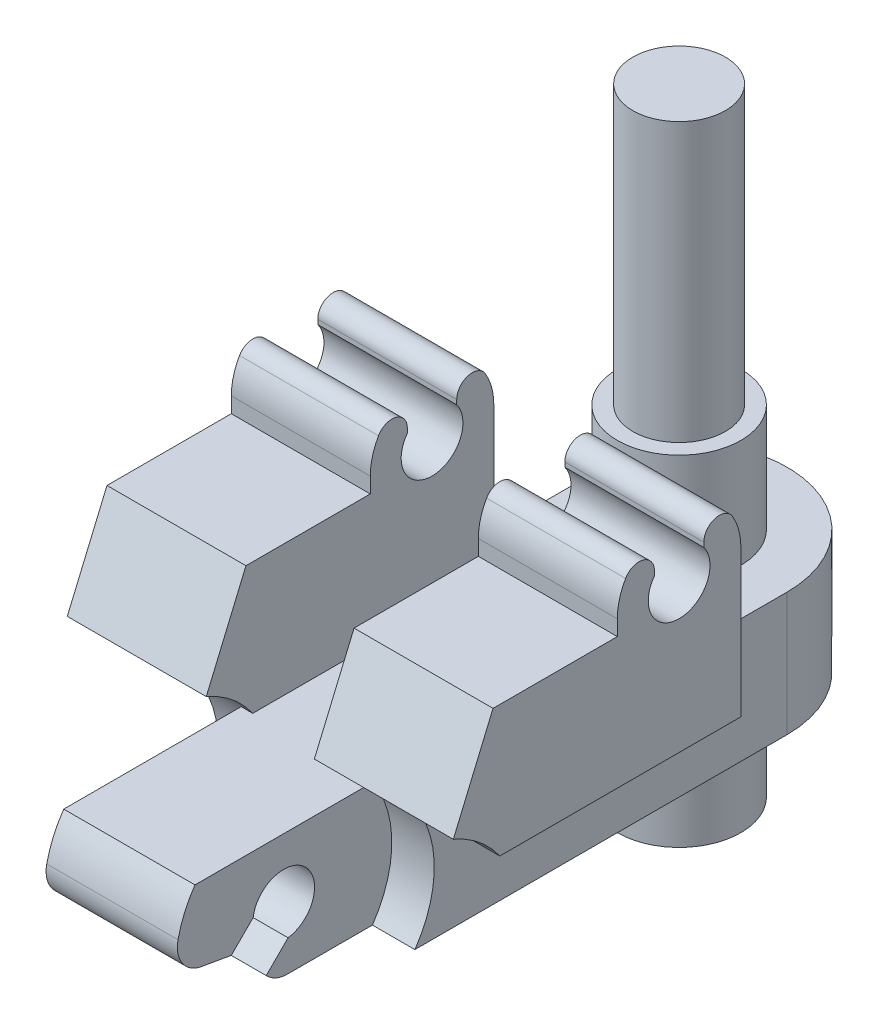
SolidWorks part; units mm, degrees
ref_plane "Front Plane" through (0, 0, 0) normal (0, 0, 1) x (1, 0, 0)
ref_plane "Top Plane" through (0, 0, 0) normal (0, 1, 0) x (1, 0, 0)
ref_plane "Right Plane" through (0, 0, 0) normal (1, 0, 0) x (0, 0, -1)
sketch "Sketch3" plane through (0, 0, 0) normal (1, 0, 0) x (0, 0, -1)
  line L0 (0.2828, -1.9799) -> (-1.9799, 0.2828)
  line L1 (0.2828, -1.9799) -> (-1.1314, -3.3941)
  line L2 (-1.1314, -3.3941) -> (-0.8188, -5.1668)
  line L3 (-0.8188, -5.1668) -> (-2.2728, -6.6208)
  line L4 (-1.9799, 0.2828) -> (-3.3941, -1.1314)
  line L5 (-3.3941, -1.1314) -> (-5.1668, -0.8188)
  line L6 (-5.1668, -0.8188) -> (-6.6208, -2.2728)
  line L7 (-0.8485, -0.8485) -> (0, 0) construction
  line L8 (0, 0) -> (-2, 0) construction
  line L9 (-1.9799, 0.2828) -> (-5.1668, -0.8188) construction
  line L10 (-0.8188, -5.1668) -> (0.2828, -1.9799) construction
  circle A0 centre (0, 0) radius 2
  circle A1 centre (0, 0) radius 6 construction
  circle A2 centre (0, 0) radius 6.5 construction
  circle A3 centre (0, 0) radius 7
  dimension "D1" = 4
  dimension "D2" = 12
  dimension "D3" = 5
  dimension "D4" = 0.5
  dimension "D5" = 2
  dimension "D7" = 3.2
  dimension "D6" = 1.8
  dimension "D8" = 45
  dimension "D9" = 125
extrude "Boss-Extrude1" add sketch "Sketch3" along normal mid plane 8.5 contours A3 L6 L5 L4 A0 L1 L2 L3 | A3 region at (0, -1.4401, -1.6605)
sketch "Sketch5" plane through (0, 0, 0) normal (1, 0, 0) x (0, 0, -1)
  line L0 (0, 7) -> (29.856, 7)
  line L1 (29.856, 7) -> (29.856, -7)
  line L2 (29.856, -7) -> (0, -7)
  arc A0 (-2.2728, -6.6208) -> (-6.6208, -2.2728) centre (0, 0) ccw construction
  arc A1 (0, -7) -> (0, 7) centre (0, 0) ccw
  dimension "D1" = 29.856
extrude "Boss-Extrude2" add sketch "Sketch5" along normal mid plane 14
sketch "Sketch6" plane through (0, 7, 0) normal (0, 1, 0) x (1, 0, 0)
  line L0 (7, 29.856) -> (-7, 29.856) construction
  circle A0 centre (0, 29.856) radius 7
extrude "Boss-Extrude3" add sketch "Sketch6" against normal up to surface (14 mm away) up to face at (0, -7, -9.952)
sketch "Sketch7" plane through (0, 0, 0) normal (0, 1, 0) x (1, 0, 0)
  circle A0 centre (0, 29.856) radius 4
  dimension "D1" = 8
extrude "Boss-Extrude4" add sketch "Sketch7" along normal blind 11 and the other way blind 11
sketch "Sketch22" plane through (0, 11, 0) normal (0, 1, 0) x (1, 0, 0)
  circle A0 centre (0, 29.856) radius 3
  dimension "D1" = 6
extrude "Boss-Extrude6" add sketch "Sketch22" along normal blind 18
sketch "Sketch8" plane through (0, 7, 0) normal (0, 1, 0) x (1, 0, 0)
  line L0 (4.25, -7) -> (4.25, 0) construction
  line L1 (-4.25, 0) -> (-4.25, -7) construction
  line L3 (7, 0) -> (7, 29.856) construction
  line L4 (-7, 29.856) -> (-7, 0) construction
  line L5 (-7, 0) -> (-4.25, 0) construction
  line L6 (4.25, 0) -> (7, 0) construction
  line L7 (4.25, -7) -> (4.25, 0)
  line L8 (-4.25, 0) -> (-4.25, -7)
  line L9 (-4.25, -7) -> (4.25, -7)
  line L10 (7, 0) -> (7, 29.856)
  line L11 (-7, 29.856) -> (-7, 0)
  line L12 (-7, 0) -> (-4.25, 0)
  line L13 (4.25, 0) -> (7, 0)
  arc A0 (7, 29.856) -> (-7, 29.856) centre (0, 29.856) ccw construction
  arc A1 (7, 29.856) -> (-7, 29.856) centre (0, 29.856) ccw
  circle M9 centre (0, 29.856) radius 4
  line M10 (7, 0) -> (7, 29.856)
  arc M11 (7, 29.856) -> (-7, 29.856) centre (0, 29.856) ccw
  line M12 (-7, 29.856) -> (-7, 0)
  line M13 (-7, 0) -> (-4.25, 0)
  line M14 (-4.25, 0) -> (4.25, 0)
  line M15 (4.25, 0) -> (7, 0)
extrude "Cut-Extrude2" cut sketch "Sketch8" against normal offset from surface (3 mm away) 4 contours M15 M10 M11 M12 M13 M14 M9 | L8 L9 L7 M14 region at (0, 7, 3.5) region at (0, 7, -16.3386) up to plane "Top Plane"
sketch "Sketch9" plane through (0, -7, 0) normal (0, -1, 0) x (1, 0, 0)
  line L7 (4.25, 0) -> (4.25, 7)
  line L8 (7, 0) -> (4.25, 0)
  line L9 (7, -29.856) -> (7, 0)
  line L10 (-7, 0) -> (-7, -29.856)
  line L11 (-4.25, 0) -> (-7, 0)
  line L12 (-4.25, 7) -> (-4.25, 0)
  line L13 (4.25, 7) -> (-4.25, 7)
  line L14 (4.25, 0) -> (4.25, 7)
  line L15 (7, 0) -> (4.25, 0)
  line L16 (7, -29.856) -> (7, 0)
  line L17 (-7, 0) -> (-7, -29.856)
  line L18 (-4.25, 0) -> (-7, 0)
  line L19 (-4.25, 7) -> (-4.25, 0)
  line L20 (4.25, 7) -> (-4.25, 7)
  arc A1 (-7, -29.856) -> (7, -29.856) centre (0, -29.856) ccw
  arc A2 (-7, -29.856) -> (7, -29.856) centre (0, -29.856) ccw
  circle M9 centre (0, -29.856) radius 4
  line M10 (-7, 0) -> (-7, -29.856)
  arc M11 (-7, -29.856) -> (7, -29.856) centre (0, -29.856) ccw
  line M12 (7, -29.856) -> (7, 0)
  line M13 (7, 0) -> (4.25, 0)
  line M14 (4.25, 0) -> (-4.25, 0)
  line M15 (-4.25, 0) -> (-7, 0)
  dimension "D1" = 0
extrude "Cut-Extrude4" cut sketch "Sketch9" against normal offset from surface (3 mm away) 4 contours M15 M10 M11 M12 M13 M14 M9 | L14 L20 L19 M14 region at (0, -7, 3.5) region at (0, -7, -16.3386) up to plane "Top Plane"
sketch "Sketch10" plane through (0, 0, 0) normal (1, 0, 0) x (0, 0, -1)
  line L3 (5.7446, -4) -> (29.856, -4)
  line L4 (29.856, -4) -> (29.856, 4)
  line L5 (29.856, 4) -> (5.7446, 4)
  line L10 (13.356, 12.5) -> (13.356, 17.5) construction
  line L11 (13.356, 17.5) -> (21.356, 17.5) construction
  line L12 (21.356, 17.5) -> (21.356, 4) construction
  line L13 (5.3059, 12.5) -> (13.356, 12.5)
  line L14 (0, 0) -> (2.7351, 6.4435) construction
  line L15 (2.7351, 6.4435) -> (5.3059, 12.5)
  line L16 (29.856, 4) -> (5.7446, 4) construction
  line L17 (21.356, 4) -> (5.7446, 4)
  line L18 (13.356, 13.5) -> (21.356, 13.5) construction
  line L19 (29.856, 11) -> (29.856, 4) construction
  line L20 (33.856, 11) -> (25.856, 11) construction
  line L21 (15.756, 14.7) -> (18.956, 14.7) construction
  line L22 (18.956, 14.7) -> (18.956, 17.1661)
  line L23 (15.756, 17.1661) -> (15.756, 14.7)
  line L24 (13.356, 13.5) -> (13.356, 12.5)
  line L25 (21.356, 13.5) -> (21.356, 4)
  arc A0 (15.756, 14.7) -> (18.956, 14.7) centre (17.356, 13.5) ccw
  arc A1 (5.7446, -4) -> (5.7446, 4) centre (0, 0) ccw
  arc A2 (5.7446, 4) -> (2.7351, 6.4435) centre (0, 0) ccw
  arc A3 (21.356, 13.5) -> (18.956, 17.1661) centre (17.356, 13.5) ccw
  arc A4 (15.756, 17.1661) -> (13.356, 13.5) centre (17.356, 13.5) ccw
  dimension "D8" = 4
  dimension "D9" = 2
  dimension "D10" = 3.2
  dimension "D2" = 67
  dimension "D3" = 8.5
  dimension "D4" = 13.5
  dimension "D5" = 5
  dimension "D7" = 5
  dimension "D1" = 0
extrude "Boss-Extrude5" add sketch "Sketch10" along normal mid plane 25
ref_plane "Plane1" through (6, 0, 0) normal (1, 0, 0) x (0, 0, -1)
ref_plane "Plane2" through (-6, 0, 0) normal (1, 0, 0) x (0, 0, -1)
sketch "Sketch13" plane through (-6, 0, 0) normal (1, 0, 0) x (0, 0, -1)
  line L0 (0, 5) -> (33.856, 5)
  line L1 (33.856, 4) -> (33.856, 11) construction
  circle A0 centre (0, 0) radius 5 construction
  dimension "D1" = 10
ref_plane "Plane3" through (0, 0, 0) normal (0, 0, 1) x (1, 0, 0)
sketch "Sketch14" plane through (0, 0, 0) normal (0, 0, 1) x (1, 0, 0)
  line L0 (-6.5303, 5.5303) -> (-8.0607, 4)
  line L1 (-7, 4) -> (-12.5, 4) construction
  line L2 (-5.4697, 4.4697) -> (-7, 2.9393)
  line L3 (-7, 4) -> (-7, -4) construction
  line L4 (-6.5303, 5.5303) -> (-5.4697, 4.4697) construction
  line L5 (-8.0607, 4) -> (-7, 4)
  line L6 (-7, 4) -> (-7, 2.9393)
  arc A0 (-5.4697, 4.4697) -> (-6.5303, 5.5303) centre (-6, 5) ccw
  point P14 (-6, 5)
  dimension "D1" = 1.5
  dimension "D2" = 45
sweep "Cut-Sweep1" cut profiles "Sketch14" path "Sketch13"
ref_plane "Plane4" through (0, 0, -32.856) normal (0, 0, -1) x (-1, 0, 0)
ref_plane "Plane5" through (-3, 0, 0) normal (-1, 0, 0) x (0, 0, 1)
sketch "Sketch18" plane through (0, 0, -32.856) normal (0, 0, -1) x (-1, 0, 0)
  line L0 (0, 29) -> (0, 16) construction
  line L2 (3, 29) -> (-3, 29) construction
  circle A0 centre (0, 16) radius 1.9
  dimension "D2" = 3.8
  dimension "D1" = 13
extrude "Cut-Extrude5" cut sketch "Sketch18" against normal blind 1
sketch "Sketch20" plane through (0, 11, 0) normal (0, 1, 0) x (1, 0, 0)
  line L0 (0, 25.856) -> (0, 0) construction
  line L2 (-3.5, -21.356) -> (3.5, -21.356)
  line L3 (-3.5, -21.356) -> (-3.5, 21.356)
  line L4 (-3.5, 21.356) -> (3.5, 21.356)
  line L5 (3.5, -21.356) -> (3.5, 21.356)
  line L6 (-3.5, -21.356) -> (3.5, 21.356) construction
  line L7 (-3.5, 21.356) -> (3.5, -21.356) construction
  line L8 (-5.9393, 21.356) -> (7, 21.356) construction
  circle A0 centre (0, 29.856) radius 4 construction
  circle A1 centre (0, 29.856) radius 4 construction
  dimension "D1" = 7
extrude "Cut-Extrude7" cut sketch "Sketch20" against normal up to surface (7 mm away) and the other way through all up to face at (0, 4, 0)
fillet "Fillet1" radius 1.9 2 edges at (0, -2.2728, 6.6208) (0, -4, 1.0245)
fillet "Fillet2" radius 1 4 edges at (-8, 17.1661, -18.956) (-8, 17.1661, -15.756) (8, 17.1661, -15.756) (8, 17.1661, -18.956)
